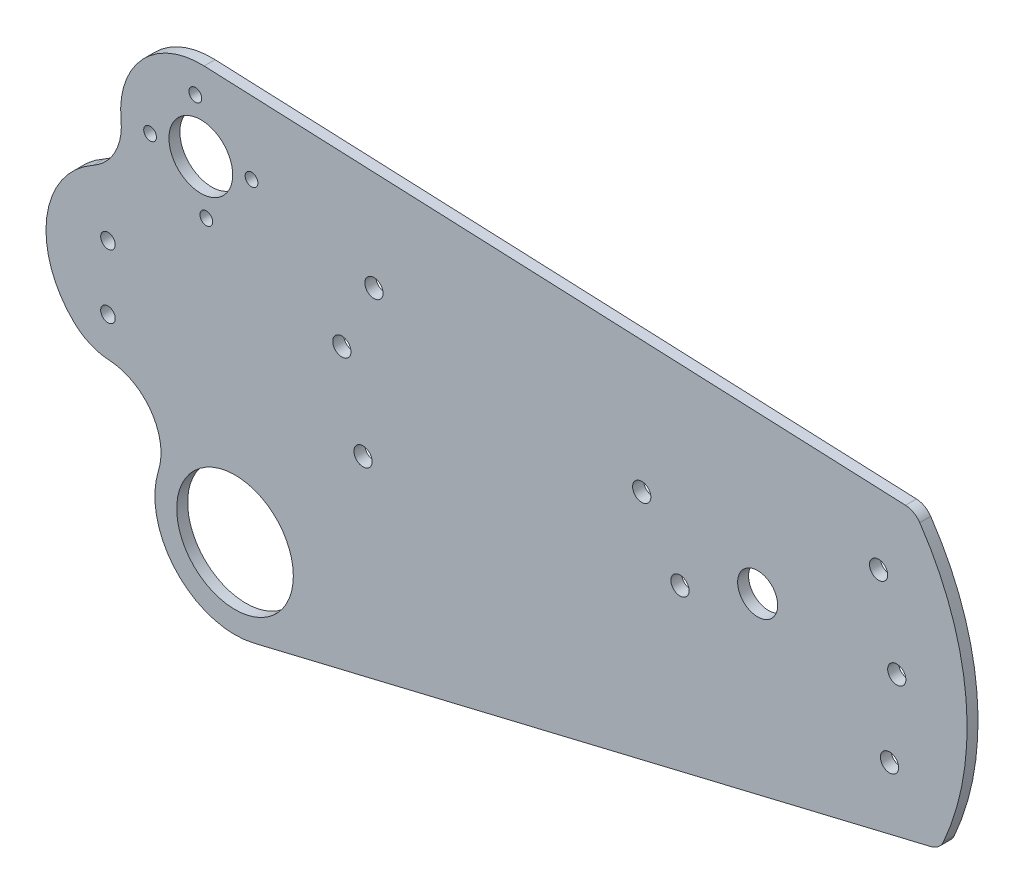
SolidWorks part; units mm, degrees
ref_plane "Front Plane" through (0, 0, 0) normal (0, 0, 1) x (1, 0, 0)
ref_plane "Top Plane" through (0, 0, 0) normal (0, 1, 0) x (1, 0, 0)
ref_plane "Right Plane" through (0, 0, 0) normal (1, 0, 0) x (0, 0, -1)
sketch "Sketch1" plane through (0, 0, 0) normal (0, 0, 1) x (1, 0, 0)
  line L0 (86.8854, -33.5) -> (-137.2004, -33.5) construction
  line L1 (-111.886, 49.4802) -> (80.595, 41.3179)
  line L2 (-115.2069, 49.6211) -> (-101.035, -81.6153) construction
  line L3 (-97.8208, -80.7688) -> (92.1699, -30.731) construction
  line L4 (78.7977, 41.3942) -> (86.7407, -32.1609) construction
  line L5 (-108.121, -15.9971) -> (82.7692, 4.6166) construction
  line L6 (91, -33.5) -> (-88.5, -33.5) construction
  line L7 (-97.4673, 5.5) -> (-155.3054, 5.5) construction
  line L8 (-138.3, -14) -> (-155.3054, -14) construction
  line L9 (-138.3, 5.5) -> (-138.3, -33.5) construction
  line L10 (-155.3054, 5.5) -> (-155.3054, -33.5) construction
  line L11 (40.0178, 33.5) -> (40.0178, -33.5) construction
  line L12 (-108.121, -83.2436) -> (87.5999, -36.3241)
  line L13 (-91.5, 33.5) -> (88, 33.5) construction
  line L14 (-68.3, -21.5) -> (-107.0746, -25.6872) construction
  circle A0 centre (40.0178, 0) radius 5.5
  circle A1 centre (-112.8181, 27.5) radius 14 construction
  circle A2 centre (-103.4238, -59.4942) radius 14 construction
  arc A3 (-91.5, 33.5) -> (-88.5, -33.5) centre (-18.0922, 3.2198) ccw construction
  circle A4 centre (-68.3, -21.5) radius 2.5
  circle A5 centre (-68.3, -21.5) radius 2.5 construction
  circle A6 centre (-138.3, -5.25) radius 2
  circle A7 centre (-138.3, -22.75) radius 2
  arc A8 (-142.3827, 10.6321) -> (-147.5429, -29.3643) centre (-130.3054, -11.2571) ccw
  arc A9 (-147.5429, -29.3643) -> (-137.2004, -33.5) centre (-137.2004, -18.5) ccw
  circle A10 centre (-112.8181, 27.5) radius 22
  arc A11 (87.5999, -36.3241) -> (91, -33.5) centre (86.4343, -31.4619) ccw
  circle A12 centre (-103.4238, -59.4942) radius 22
  arc A13 (91, -33.5) -> (84.5157, 39.1371) centre (22.6589, -2.9929) ccw
  arc A14 (91, -33.5) -> (88, 33.5) centre (22.6589, -2.9929) ccw construction
  arc A15 (84.5157, 39.1371) -> (80.595, 41.3179) centre (80.3831, 36.3224) ccw
  arc A17 (-124.4228, -52.9336) -> (-137.9704, -33.4802) centre (-138.7403, -48.4604) ccw
  arc A18 (-142.3827, 10.6321) -> (-134.7058, 25.2795) centre (-149.6292, 23.7656) ccw
  circle A19 centre (-74.1, 1.7) radius 2.5
  circle A20 centre (-65.3, 20) radius 2.5
  circle A21 centre (8.2, 8.3) radius 2.5
  circle A23 centre (18.7, -8.7) radius 2.5
  circle A25 centre (78.2, -0.1) radius 2.5
  circle A26 centre (76.2, -22) radius 2.5
  circle A27 centre (73.2, 22.3) radius 2.5
  circle A28 centre (73.2, 22.3) radius 2.5 construction
  circle A29 centre (78.2, -0.1) radius 2.5 construction
  circle A31 centre (8.2, 8.3) radius 2.5 construction
  circle A32 centre (18.7, -8.7) radius 2.5 construction
  circle A33 centre (76.2, -22) radius 2.5 construction
  circle A34 centre (-74.1, 1.7) radius 2.5 construction
  circle A35 centre (-65.3, 20) radius 2.5 construction
  circle A36 centre (-114.3212, 41.4191) radius 1.75
  circle A37 centre (-98.899, 29.0031) radius 1.75
  circle A38 centre (-111.315, 13.5809) radius 1.75
  circle A39 centre (-126.7372, 25.9969) radius 1.75
  circle A40 centre (-104.9269, -45.5752) radius 1.75
  circle A41 centre (-89.5048, -57.9912) radius 1.75
  circle A42 centre (-101.9208, -73.4133) radius 1.75
  circle A43 centre (-117.3429, -60.9973) radius 1.75
  circle A44 centre (40.0178, 0) radius 35 construction
  circle A45 centre (40.0178, 0) radius 43
  circle A49 centre (-103.4238, -59.4942) radius 16
  circle A50 centre (-112.8181, 27.5) radius 16 construction
  circle A51 centre (-112.8181, 27.5) radius 8.75
  circle A52 centre (-103.4238, -59.4942) radius 8.75
  arc A53 (91, -33.5) -> (88, 33.5) centre (22.6589, -2.9929) ccw construction
  point P52 (82.7692, 4.6166)
  point P109 (-112.8181, 27.5)
  point P118 (-103.4238, -59.4942)
  dimension "D5" = 4
  dimension "D6" = 25
  dimension "D9" = 15
  dimension "D13" = 10
  dimension "D14" = 28
  dimension "D11" = 44
  dimension "D15" = 3.5
  dimension "D12" = 70
  dimension "D19" = 11
  dimension "D20" = 17.5
  dimension "D22" = 32
  dimension "D2" = 39
  dimension "D3" = 70
  dimension "D4" = 17.5
  dimension "D7" = 14
  dimension "D8" = 10
  dimension "D10" = 87.5
  dimension "D21" = 192
  dimension "D23" = 39
  dimension "D18" = 8
  dimension "D16" = 4
  dimension "D17" = 4
extrude "Boss-Extrude1" add sketch "Sketch1" along normal blind 3 contours A45 A0 A25 A26 A27 | A45 L1 A10 A18 A8 A9 A17 A12 L3 A23 A21 A20 A19 A7 A6 A4 | A10 A39 A38 A37 A36 | A12 A49 region at (70.1828, 28.9129, 0) region at (-43.9999, -9.8567, 0) region at (-97.3849, 42.2927, 0) region at (-100.1994, -38.3611, 0)
